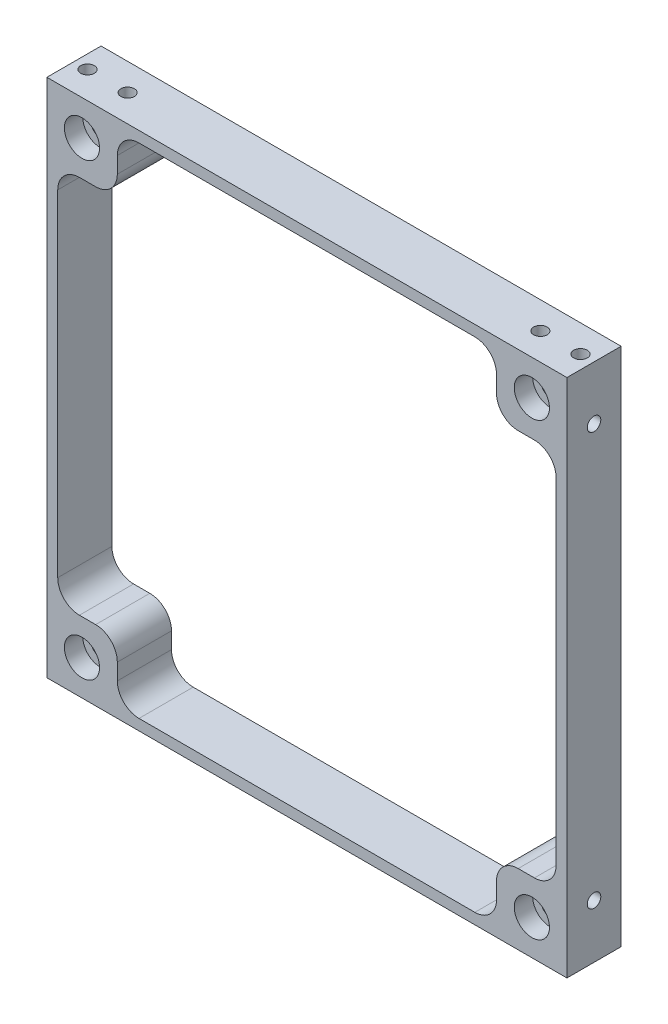
SolidWorks part; units mm, degrees
material "7075-T6 (SN)"
ref_plane "Front Plane" through (0, 0, 0) normal (0, 0, 1) x (1, 0, 0)
ref_plane "Top Plane" through (0, 0, 0) normal (0, 1, 0) x (1, 0, 0)
ref_plane "Right Plane" through (0, 0, 0) normal (1, 0, 0) x (0, 0, -1)
sketch "Construction Lines" plane through (0, 0, 0) normal (0, 0, 1) x (1, 0, 0)
  line L0 (0, 0) -> (0, -14.7163) construction
  line L1 (0, 0) -> (23.9312, 0) construction
sketch "Sketch3" plane through (0, 0, 0) normal (0, 0, 1) x (1, 0, 0)
  line L0 (0, 48) -> (48, 48)
  line L1 (0, 200000) -> (0, -200014.7163) construction
  line L2 (48, 48) -> (48, 0)
  line L3 (-200000, 0) -> (200023.9312, 0) construction
  line L4 (0, 46) -> (31, 46)
  line L5 (46, 31) -> (46, 0)
  line L6 (0, 48) -> (0, 46)
  line L7 (48, 0) -> (46, 0)
  line L8 (35, 42) -> (35, 39)
  line L9 (39, 35) -> (42, 35)
  line L11 (0, 46) -> (46, 46) construction
  line L12 (46, 46) -> (46, 0) construction
  arc A0 (31, 46) -> (35, 42) centre (31, 42) cw
  arc A1 (35, 39) -> (39, 35) centre (39, 39) ccw
  arc A2 (46, 31) -> (42, 35) centre (42, 31) ccw
  dimension "D6" = 4
  dimension "D1" = 48
  dimension "D2" = 48
  dimension "D4" = 13
  dimension "D5" = 13
  dimension "D3" = 2
extrude "BottomLayer" add sketch "Sketch3" along normal blind 10
sketch "TopHolePosition" plane through (0, 0, 10) normal (0, 0, 1) x (1, 0, 0)
  line L0 (0, 0) -> (48, 48) construction
sketch "HolePosition" plane through (0, 0, 10) normal (0, 0, 1) x (1, 0, 0)
  line L0 (0, 41.525) -> (41.525, 41.525) construction
  line L1 (0, 200000) -> (0, -200014.7163) construction
  line L2 (0, 0) -> (48, 48) construction
  line L3 (41.525, 41.525) -> (41.525, 0) construction
  line L4 (-200000, 0) -> (200023.9312, 0) construction
  dimension "D1" = 41.525
hole_wizard "CBORE for M3 Hex Socket Head Cap Screw1" positions "Sketch13" profile "Sketch14" counterbore size "M3" standard "ISO" end condition through all
sketch "Sketch13" plane through (0, 0, 10) normal (0, 0, 1) x (1, 0, 0)
  point P0 (41.525, 41.525)
sketch "Sketch14" plane through (41.525, 41.525, 10) normal (1, 0, 0) x (0, -1, 0)
  line L0 (0, 0) -> (0, 10)
  line L1 (0, 10) -> (1.7, 10)
  line L3 (1.7, 10) -> (1.7, 3.4)
  line L4 (1.7, 3.4) -> (3.25, 3.4)
  line L5 (3.25, 3.4) -> (3.25, 0)
  line L7 (3.25, 0) -> (0, 0)
  line L11 (0, -6.35) -> (0, 107.95) construction
  dimension "Thru Hole Dia." = 3.4
  dimension "Thru Hole Depth" = 10
  dimension "C'Bore Dia." = 6.5
  dimension "C'Bore Depth" = 3.4
ref_axis "Axis1" through (0, 0, -0.5) along (0, 0, 1)
pattern_circular "CirPattern1" count 4 over 360 about axis through (0, 0, -0.5) along (0, 0, 1) of "BottomLayer", "CBORE for M3 Hex Socket Head Cap Screw1"
sketch "SidePlate Hole ZY" plane through (48, 0, 0) normal (1, 0, 0) x (0, 0, -1)
  line L0 (-5, 48) -> (-5, -48) construction
  line L1 (-10, 48) -> (0, 48) construction
  line L2 (-10, -48) -> (0, -48) construction
  line L3 (-10, 38.1) -> (-5, 38.1) construction
  line L5 (-10, -48) -> (-10, 48) construction
  dimension "D1" = 9.9
sketch "SidePlate&RailHole ZX" plane through (0, 48, 0) normal (0, 1, 0) x (1, 0, 0)
  line L0 (48, -5) -> (-48, -5) construction
  line L1 (-48, -10) -> (-48, 0) construction
  line L2 (45.5, -10) -> (45.5, -5) construction
  line L3 (48, -10) -> (-48, -10) construction
  line L7 (38.1, -10) -> (38.1, -5) construction
  line L8 (48, -10) -> (48, 0) construction
  dimension "D1" = 2.5
  dimension "D2" = 9.9
hole_wizard "Tap Drill M3 Side Plate" positions "Sketch20" profile "Sketch21" hole size "M3" standard "ISO"
sketch "Sketch20" plane through (48, 0, 0) normal (1, 0, 0) x (0, 0, -1)
  point P0 (-5, 38.1)
sketch "Sketch21" plane through (48, 38.1, 5) normal (0, 1, 0) x (0, 0, -1)
  line L0 (0, 0) -> (0, 5.7511)
  line L1 (0, 5.7511) -> (1.25, 5)
  line L2 (1.25, 5) -> (1.25, 0)
  line L5 (1.25, 0) -> (0, 0)
  line L10 (0, 5.7511) -> (-1.25, 5) construction
  line L11 (0, -6.35) -> (0, 107.95) construction
  dimension "Hole Dia." = 2.5
  dimension "Hole Depth" = 5
  dimension "Drill Angle" = 118
hole_wizard "Tap Drill M3 Side Plate " positions "Sketch26" profile "Sketch27" hole size "M3" standard "ISO"
sketch "Sketch26" plane through (0, 48, 0) normal (0, 1, 0) x (1, 0, 0)
  point P0 (38.1, -5)
sketch "Sketch27" plane through (38.1, 48, 5) normal (1, 0, 0) x (0, 0, 1)
  line L0 (0, 0) -> (0, 5.7511)
  line L1 (0, 5.7511) -> (1.25, 5)
  line L2 (1.25, 5) -> (1.25, 0)
  line L5 (1.25, 0) -> (0, 0)
  line L10 (0, 5.7511) -> (-1.25, 5) construction
  line L11 (0, -6.35) -> (0, 107.95) construction
  dimension "Hole Dia." = 2.5
  dimension "Hole Depth" = 5
  dimension "Drill Angle" = 118
hole_wizard "Tap Drill M3 Rail" positions "Sketch28" profile "Sketch29" hole size "M3" standard "ISO"
sketch "Sketch28" plane through (0, 48, 0) normal (0, 1, 0) x (1, 0, 0)
  point P0 (45.5, -5)
sketch "Sketch29" plane through (45.5, 48, 5) normal (1, 0, 0) x (0, 0, 1)
  line L0 (0, 0) -> (0, 5.7511)
  line L1 (0, 5.7511) -> (1.25, 5)
  line L2 (1.25, 5) -> (1.25, 0)
  line L5 (1.25, 0) -> (0, 0)
  line L10 (0, 5.7511) -> (-1.25, 5) construction
  line L11 (0, -6.35) -> (0, 107.95) construction
  dimension "Hole Dia." = 2.5
  dimension "Hole Depth" = 5
  dimension "Drill Angle" = 118
mirror "SidePlate and Rail Holes 1" about plane through (0, 0, 0) normal (1, 0, 0) of "Tap Drill M3 Side Plate", "Tap Drill M3 Rail", "Tap Drill M3 Side Plate "
mirror "Side Plate and Rail Holes 2" about plane through (0, 0, 0) normal (0, 1, 0) of "SidePlate and Rail Holes 1"
sketch "Sketch30" plane through (0, 0, 0) normal (0, 0, -1) x (-1, 0, 0)
  circle A1 centre (-41.525, 41.525) radius 3.25
  point P0 (-41.525, 41.525)
extrude "Cut-Extrude1" cut sketch "Sketch30" against normal blind 3.4
pattern_circular "CirPattern2" count 4 over 360 about axis through (0, 0, -0.5) along (0, 0, 1) of "Cut-Extrude1"
